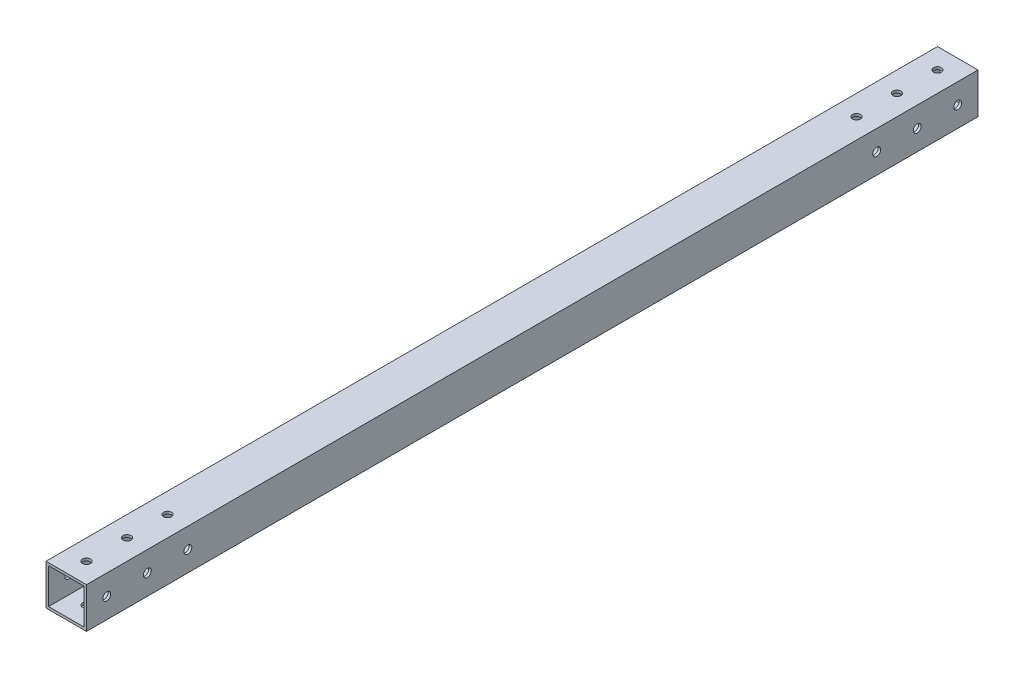
SolidWorks part; units mm, degrees
material "6061-T6 (SS)"
ref_plane "Front Plane" through (0, 0, 0) normal (0, 0, 1) x (1, 0, 0)
ref_plane "Top Plane" through (0, 0, 0) normal (0, 1, 0) x (1, 0, 0)
ref_plane "Right Plane" through (0, 0, 0) normal (1, 0, 0) x (0, 0, -1)
sketch "Sketch1" plane through (0, 0, 0) normal (0, 0, 1) x (1, 0, 0)
  line L1 (0, 0) -> (25.4, 0)
  line L2 (0, 0) -> (0, 25.4)
  line L3 (0, 25.4) -> (25.4, 25.4)
  line L4 (25.4, 0) -> (25.4, 25.4)
  dimension "D1" = 25.4
  dimension "D2" = 25.4
extrude "Boss-Extrude1" add sketch "Sketch1" along normal mid plane 558.8
sketch "Sketch2" plane through (0, 25.4, 0) normal (0, 1, 0) x (1, 0, 0)
  line L0 (25.4, -279.4) -> (0, -279.4) construction
  line L1 (0, -279.4) -> (0, 279.4) construction
  circle A0 centre (12.7, -266.7) radius 2.4892
  circle A1 centre (12.7, -241.3) radius 2.4892
  circle A2 centre (12.7, -215.9) radius 2.4892
  point P10 (0, 0)
  dimension "D1" = 4.9784
  dimension "D2" = 25.4
  dimension "D3" = 25.4
  dimension "D4" = 12.7
  dimension "D5" = 12.7
sketch "Sketch3" plane through (0, 0, 0) normal (-1, 0, 0) x (0, 0, 1)
  line L0 (279.4, 0) -> (-279.4, 0) construction
  line L1 (279.4, 25.4) -> (279.4, 0) construction
  circle A0 centre (266.7, 12.7) radius 2.4892
  circle A1 centre (241.3, 12.7) radius 2.4892
  circle A2 centre (215.9, 12.7) radius 2.4892
  point P6 (0, 0)
  point P11 (278.4549, 15.5921)
  dimension "D1" = 4.9784
  dimension "D2" = 12.7
  dimension "D3" = 12.7
  dimension "D4" = 25.4
  dimension "D5" = 25.4
shell "Shell1" thickness 1.5875 removed face at (12.7, 12.7, 279.4) removed face at (12.7, 12.7, -279.4)
extrude "Cut-Extrude1" cut sketch "Sketch2" against normal through all
extrude "Cut-Extrude2" cut sketch "Sketch3" against normal through all
mirror "Mirror1" about plane through (0, 0, 0) normal (0, 0, 1) of "Cut-Extrude1", "Cut-Extrude2"
